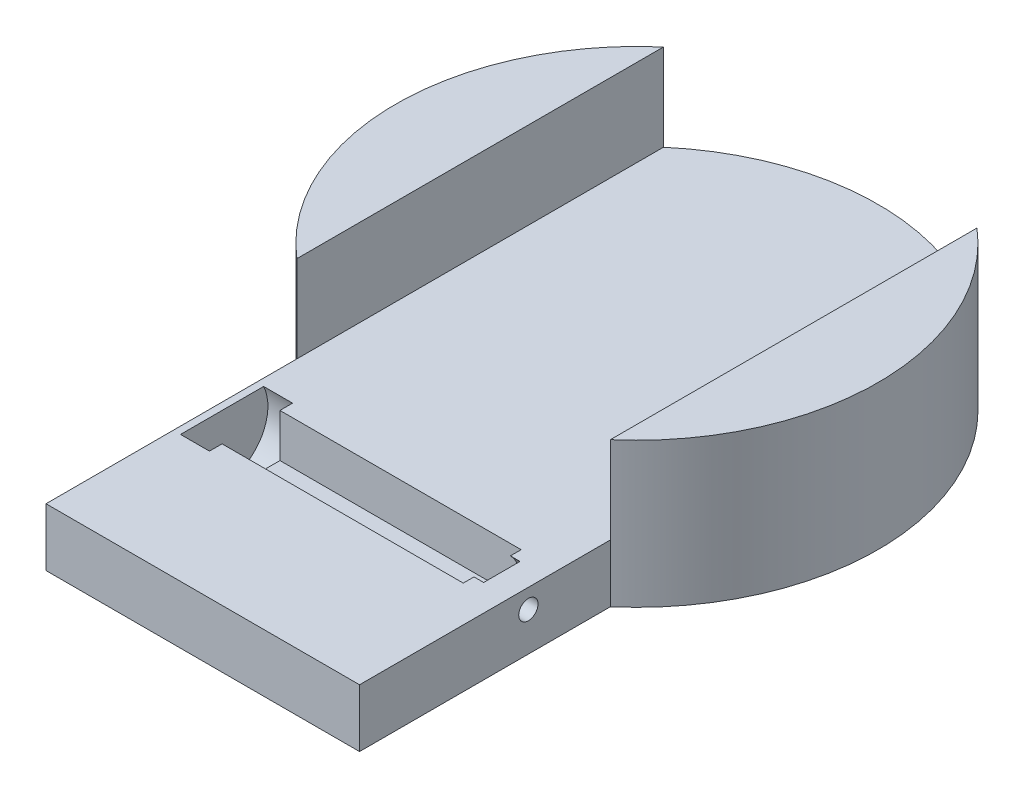
SolidWorks part; units mm, degrees
ref_plane "Front Plane" through (0, 0, 0) normal (0, 0, 1) x (1, 0, 0)
ref_plane "Top Plane" through (0, 0, 0) normal (0, 1, 0) x (1, 0, 0)
ref_plane "Right Plane" through (0, 0, 0) normal (1, 0, 0) x (0, 0, -1)
sketch "Sketch1" plane through (0, 0, 0) normal (0, 1, 0) x (1, 0, 0)
  circle A0 centre (0, 0) radius 50
  dimension "D1" = 100
extrude "Boss-Extrude1" add sketch "Sketch1" along normal blind 30
sketch "Sketch2" plane through (0, 0, 0) normal (0, -1, 0) x (1, 0, 0)
  line L0 (-2, 1.5) -> (-2, -1.5)
  circle A0 centre (0, 0) radius 4.4
  circle A1 centre (0, 0) radius 2.5
  dimension "D1" = 8.8
  dimension "D2" = 5
  dimension "D3" = 2
extrude "Boss-Extrude2" add sketch "Sketch2" along normal blind 10 contours A0 A1 | L0 A1 region at (-2.2018, 0, 0) region at (-4.2755, 0, 0)
sketch "Sketch3" plane through (0, 0, 0) normal (0, -1, 0) x (1, 0, 0)
  circle A0 centre (0, 0) radius 7.5
  circle A1 centre (0, 0) radius 4.4
  circle M2 centre (0, 0) radius 4.4
  dimension "D1" = 15
extrude "Boss-Extrude3" add sketch "Sketch3" along normal blind 2 contours A0 M2 region at (-7.2879, 0, 0)
sketch "Sketch4" plane through (0, 30, 0) normal (0, 1, 0) x (1, 0, 0)
  line L1 (32.5, 50) -> (-32.5, 50)
  line L2 (32.5, 50) -> (32.5, -50)
  line L4 (-32.5, 50) -> (-32.5, -50)
  line L5 (32.5, 50) -> (-32.5, -50) construction
  line L6 (32.5, -50) -> (-32.5, 50) construction
  line L8 (-32.5, -50) -> (32.5, -50)
  point P0 (0, 0)
  dimension "D1" = 65
  dimension "D2" = 100
extrude "Cut-Extrude1" cut sketch "Sketch4" against normal offset from surface (18 mm away) 12 up to face at (0, 0, 7.5)
ref_plane "Plane1" through (0, 12, 50) normal (0, 0, 1) x (1, 0, 0)
sketch "Sketch5" plane through (0, 12, 50) normal (0, 0, 1) x (1, 0, 0)
  line L0 (-50, -12) -> (50, -12) construction
  line L1 (-32.5, 0) -> (32.5, 0)
  line L2 (-32.5, 0) -> (-32.5, -12)
  line L3 (-32.5, -12) -> (32.5, -12)
  line L4 (32.5, 0) -> (32.5, -12)
  line L5 (-32.5, 0) -> (32.5, -12) construction
  line L6 (-32.5, -12) -> (32.5, 0) construction
  point P4 (0, -6)
extrude "Boss-Extrude4" add sketch "Sketch5" along normal blind 40 separate body
sketch "Sketch6" plane through (0, 0, 50) normal (0, 0, -1) x (-1, 0, 0)
  line L1 (-32.5, 12) -> (32.5, 12)
  line L2 (-32.5, 12) -> (-32.5, 0)
  line L3 (-32.5, 0) -> (32.5, 0)
  line L4 (32.5, 12) -> (32.5, 0)
  line L5 (-32.5, 12) -> (32.5, 0) construction
  line L6 (-32.5, 0) -> (32.5, 12) construction
  point P4 (0, 6)
extrude "Boss-Extrude5" add sketch "Sketch6" along normal up to surface up to face at (0, 21, 0)
sketch "Sketch7" plane through (0, 12, 0) normal (0, 1, 0) x (1, 0, 0)
  line L0 (0, 0) -> (0, -90) construction
  line L1 (25, -49) -> (-25, -49)
  line L2 (25, -49) -> (25, -61)
  line L3 (25, -61) -> (-25, -61)
  line L4 (-25, -49) -> (-25, -61)
  line L5 (25, -49) -> (-25, -61) construction
  line L6 (25, -61) -> (-25, -49) construction
  line L7 (32.5, -90) -> (-32.5, -90) construction
  point P0 (0, -55)
  dimension "D1" = 50
  dimension "D2" = 55
  dimension "D3" = 12
extrude "Cut-Extrude2" cut sketch "Sketch7" against normal offset from surface (9 mm away) 3 up to face at (0.25, 0, 0)
sketch "Sketch8" plane through (-25, 0, 0) normal (1, 0, 0) x (0, 0, -1)
  circle A0 centre (-55, 8) radius 9.5
  dimension "D1" = 19
extrude "Cut-Extrude3" cut sketch "Sketch8" against normal blind 6
sketch "Sketch9" plane through (25, 0, 0) normal (-1, 0, 0) x (0, 0, 1)
  circle A0 centre (55, 8) radius 2
  dimension "D1" = 4
extrude "Cut-Extrude4" cut sketch "Sketch9" against normal up to surface (7.5 mm away) up to face at (32.5, 6, 63.9984)
sketch "Sketch10" plane through (25, 0, 0) normal (-1, 0, 0) x (0, 0, 1)
  circle A0 centre (55, 8) radius 5.5
  dimension "D1" = 11
extrude "Cut-Extrude5" cut sketch "Sketch10" against normal blind 2 and the other way blind 1
sketch "Sketch11" plane through (32.5, 0, 0) normal (1, 0, 0) x (0, 0, -1)
  circle A0 centre (-55, 8) radius 12 construction
  dimension "D1" = 24
